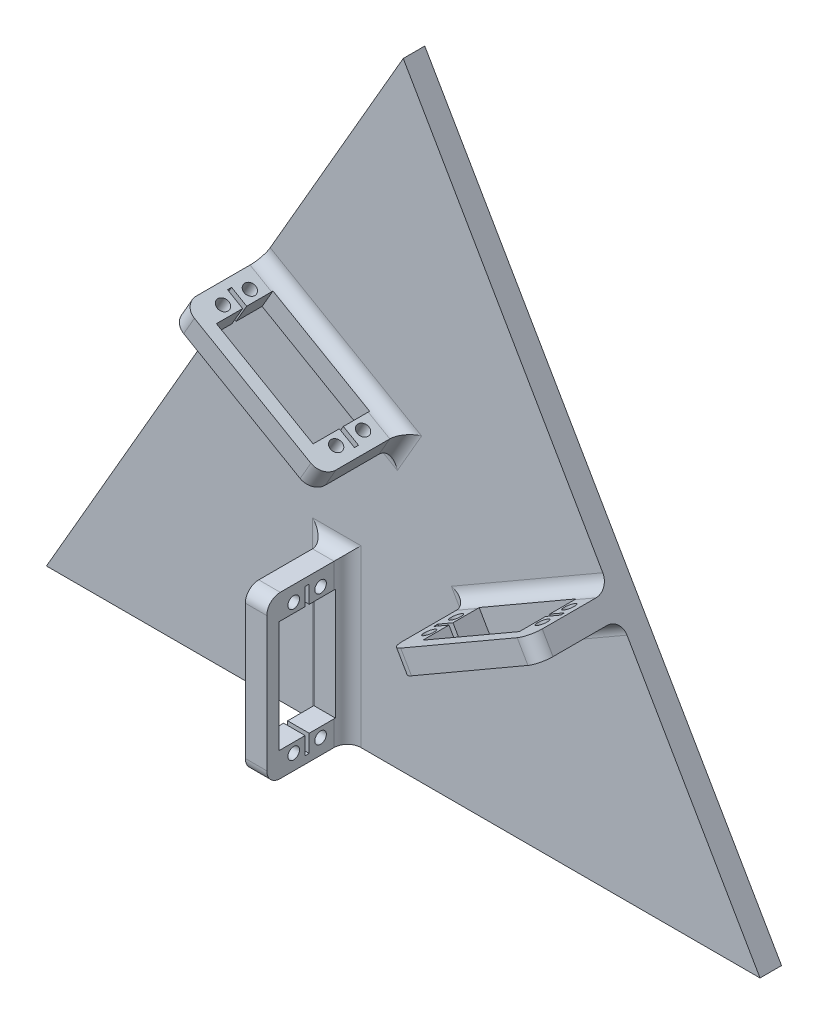
SolidWorks part; units mm, degrees
ref_plane "Front Plane" through (0, 0, 0) normal (1, 0, 0) x (0, 1, 0)
ref_plane "Top Plane" through (0, 0, 0) normal (0, 0, 1) x (0, 1, 0)
ref_plane "Right Plane" through (0, 0, 0) normal (0, 1, 0) x (-1, 0, 0)
sketch "Sketch1" plane through (0, 0, 0) normal (0, 0, 1) x (0, 1, 0)
  line L0 (0, 0) -> (49.7618, 86.19)
  line L1 (49.7618, 86.19) -> (99.5236, 0)
  line L2 (99.5236, 0) -> (0, 0)
  line L3 (63.1745, 109.4215) -> (49.7618, 86.19)
  line L4 (63.1745, 109.4215) -> (112.9364, 80.6915)
  line L5 (112.9364, 80.6915) -> (82.9364, 28.73)
  line L6 (99.5236, 0) -> (112.9364, -23.2315)
  line L7 (112.9364, -23.2315) -> (63.1745, -51.9615)
  line L8 (63.1745, -51.9615) -> (33.1745, 0)
  line L9 (0, 0) -> (-26.8255, 0)
  line L10 (-26.8255, 0) -> (-26.8255, 57.46)
  line L11 (-26.8255, 57.46) -> (33.1745, 57.46)
  line L12 (88.0555, 95.0565) -> (18.5216, -25.3796) construction
  line L13 (88.0555, -37.5965) -> (-9.2616, 130.9616) construction
  line L14 (-26.8255, 28.73) -> (138.1161, 28.73) construction
  dimension "D1" = 28.73
  dimension "D3" = 60
extrude "Boss-Extrude1" add sketch "Sketch1" along normal blind 8 contours L5 L4 L3 L1 | L11 L10 L9 L0 | L8 L7 L6 L2 | L2 L0 L1 region at (-32.3891, -4.0628, 0) region at (19.713, 73.5053, 0) region at (-73.5139, 79.843, 0)
sketch "Sketch2" plane through (0, 0, 8) normal (0, 0, 1) x (1, 0, 0)
  line L18 (-80.6915, 112.9364) -> (-28.73, 82.9364)
  line L19 (-28.73, 82.9364) -> (-32.73, 76.0082)
  line L20 (-32.73, 76.0082) -> (-84.6915, 106.0082)
  line L21 (-109.4215, 63.1745) -> (-80.6915, 112.9364) construction
  line L22 (-84.6915, 106.0082) -> (-80.6915, 112.9364)
  line L23 (51.9615, 63.1745) -> (0, 33.1745)
  line L24 (0, 33.1745) -> (-4, 40.1027)
  line L25 (-4, 40.1027) -> (47.9615, 70.1027)
  line L26 (23.2315, 112.9364) -> (51.9615, 63.1745) construction
  line L27 (47.9615, 70.1027) -> (51.9615, 63.1745)
  line L28 (-57.46, -26.8255) -> (-57.46, 33.1745)
  line L29 (-57.46, 33.1745) -> (-49.46, 33.1745)
  line L30 (-49.46, 33.1745) -> (-49.46, -26.8255)
  line L31 (0, -26.8255) -> (-57.46, -26.8255) construction
  line L32 (-49.46, -26.8255) -> (-57.46, -26.8255)
  line M5 (-28.73, 82.9364) -> (-80.6915, 112.9364)
  line M6 (-80.6915, 112.9364) -> (-109.4215, 63.1745)
  line M8 (-57.46, 33.1745) -> (-57.46, -26.8255)
  line M9 (-57.46, -26.8255) -> (0, -26.8255)
  line M11 (0, 33.1745) -> (51.9615, 63.1745)
  line M12 (51.9615, 63.1745) -> (23.2315, 112.9364)
  dimension "D1" = 8
extrude "Boss-Extrude2" add sketch "Sketch2" along normal blind 30 contours L20 L19 M5 M6 | L25 L24 M11 M12 | L30 L29 M8 M9 region at (-56.7108, 94.4723, 8) region at (23.9808, 51.6386, 8) region at (-53.46, 3.1745, 8)
sketch "Sketch3" plane through (-135.5994, 135.3999, 0) normal (-0.5, -0.866, 0) x (0.866, -0.5, 0)
  line L0 (109.5334, 23.75) -> (116.0334, 23.75)
  line L1 (64.4834, 28) -> (113.0834, 28) construction
  line L2 (64.4834, 28) -> (64.4834, 18) construction
  line L3 (64.4834, 18) -> (113.0834, 18) construction
  line L4 (113.0834, 28) -> (113.0834, 18) construction
  line L5 (88.7834, 38) -> (88.7834, 8) construction
  line L6 (68.0334, 12.5) -> (109.5334, 12.5)
  line L9 (68.0334, 12.5) -> (68.0334, 33.5)
  line L10 (68.0334, 33.5) -> (109.5334, 33.5)
  line L11 (109.5334, 12.5) -> (109.5334, 33.5)
  line L12 (58.7834, 23) -> (88.7834, 23) construction
  line L15 (68.0334, 12.5) -> (109.5334, 33.5) construction
  line L16 (68.0334, 33.5) -> (109.5334, 12.5) construction
  line L17 (61.5334, 23.75) -> (68.0334, 23.75)
  line L18 (61.5334, 23.75) -> (61.5334, 22.25)
  line L19 (61.5334, 22.25) -> (68.0334, 22.25)
  line L20 (116.0334, 23.75) -> (116.0334, 22.25)
  line L21 (109.5334, 22.25) -> (116.0334, 22.25)
  line L22 (118.7834, 38) -> (58.7834, 38) construction
  line L23 (58.7834, 38) -> (58.7834, 8) construction
  circle A0 centre (64.4834, 28) radius 2.15
  circle A1 centre (64.4834, 18) radius 2.15
  circle A2 centre (113.0834, 18) radius 2.15
  circle A3 centre (113.0834, 28) radius 2.15
  point P10 (64, 38)
  point P13 (34, 23)
  point P18 (0, 0)
  point P19 (64, 23)
  point P20 (88.7834, 28)
  point P21 (64.4834, 23)
  point P22 (88.7834, 23)
  point P31 (116.0334, 23)
  dimension "D1" = 4.3
  dimension "D2" = 10
  dimension "D3" = 48.6
  dimension "D4" = 41.5
  dimension "D5" = 21
  dimension "D6" = 1.5
  dimension "D7" = 6.5
extrude "Cut-Extrude1" cut sketch "Sketch3" against normal up to next contours L6 L11 L10 L9 | A0 | A1 | A2 | A3 | L11 L21 L20 L0 | L18 L19 L9 L17 region at (-37.9262, 79.0082, 23) region at (-58.7108, 91.0082, 23) region at (-79.4954, 103.0082, 23) region at (-79.7552, 103.1582, 28) region at (-79.7552, 103.1582, 18) region at (-37.6663, 78.8582, 18) region at (-37.6663, 78.8582, 28)
sketch "Sketch4" plane through (0.0029, 42.4138, 0) normal (-0.5, 0.866, 0) x (-0.866, -0.5, 0)
  line L0 (-25.3778, 38) -> (-25.3778, 8) construction
  line L3 (-55.3778, 23) -> (4.6222, 23) construction
  line L6 (-4.6278, 22.25) -> (1.8722, 22.25)
  line L7 (-49.6778, 18) -> (-1.0778, 18) construction
  line L8 (-49.6778, 18) -> (-49.6778, 28) construction
  line L9 (-49.6778, 28) -> (-1.0778, 28) construction
  line L10 (-1.0778, 18) -> (-1.0778, 28) construction
  line L11 (-49.6778, 18) -> (-1.0778, 28) construction
  line L12 (-49.6778, 28) -> (-1.0778, 18) construction
  line L13 (-46.1278, 12.5) -> (-4.6278, 12.5)
  line L14 (-46.1278, 12.5) -> (-46.1278, 33.5)
  line L15 (-46.1278, 33.5) -> (-4.6278, 33.5)
  line L16 (-4.6278, 12.5) -> (-4.6278, 33.5)
  line L17 (-46.1278, 12.5) -> (-4.6278, 33.5) construction
  line L18 (-46.1278, 33.5) -> (-4.6278, 12.5) construction
  line L19 (-52.6278, 23.75) -> (-46.1278, 23.75)
  line L20 (-52.6278, 23.75) -> (-52.6278, 22.25)
  line L21 (-52.6278, 22.25) -> (-46.1278, 22.25)
  line L22 (1.8722, 23.75) -> (1.8722, 22.25)
  line L23 (-4.6278, 23.75) -> (1.8722, 23.75)
  line L24 (4.6222, 38) -> (-55.3778, 38) construction
  line L25 (-55.3778, 38) -> (-55.3778, 8) construction
  circle A0 centre (-49.6778, 28) radius 2.15
  circle A1 centre (-49.6778, 18) radius 2.15
  circle A2 centre (-1.0778, 18) radius 2.15
  circle A3 centre (-1.0778, 28) radius 2.15
  point P2 (-39.923, 38)
  point P5 (-39.923, 22.1952)
  point P8 (-69.923, 23)
  point P11 (-15.623, 17.2063)
  point P12 (-25.3778, 23)
  point P21 (-25.3778, 23)
  point P30 (1.8722, 23)
  point P34 (-39.923, 23)
  dimension "D3" = 4.3
  dimension "D1" = 10
  dimension "D2" = 48.6
  dimension "D4" = 41.5
  dimension "D5" = 21
  dimension "D6" = 1.5
  dimension "D7" = 6.5
extrude "Cut-Extrude2" cut sketch "Sketch4" against normal up to next contours L13 L16 L15 L14 | A0 | A1 | L20 L21 L14 L19 | A2 | A3 | L23 L16 L6 L22 region at (1.1962, 43.1027, 23) region at (21.9808, 55.1027, 23) region at (42.7654, 67.1027, 23) region at (43.0252, 67.2527, 28) region at (43.0252, 67.2527, 18) region at (0.9363, 42.9527, 18) region at (0.9363, 42.9527, 28)
sketch "Sketch5" plane through (-49.46, -65.1325, 0) normal (1, 0, 0) x (0, 1, 0)
  line L0 (68.307, 38) -> (68.307, 8) construction
  line L3 (38.307, 23) -> (98.307, 23) construction
  line L6 (89.057, 23.75) -> (95.557, 23.75)
  line L7 (44.007, 18) -> (92.607, 18) construction
  line L8 (44.007, 18) -> (44.007, 28) construction
  line L9 (44.007, 28) -> (92.607, 28) construction
  line L10 (92.607, 18) -> (92.607, 28) construction
  line L11 (44.007, 18) -> (92.607, 28) construction
  line L12 (44.007, 28) -> (92.607, 18) construction
  line L13 (47.557, 12.5) -> (89.057, 12.5)
  line L14 (47.557, 12.5) -> (47.557, 33.5)
  line L15 (47.557, 33.5) -> (89.057, 33.5)
  line L16 (89.057, 12.5) -> (89.057, 33.5)
  line L17 (47.557, 12.5) -> (89.057, 33.5) construction
  line L18 (47.557, 33.5) -> (89.057, 12.5) construction
  line L19 (41.057, 23.75) -> (47.557, 23.75)
  line L20 (41.057, 23.75) -> (41.057, 22.25)
  line L21 (41.057, 22.25) -> (47.557, 22.25)
  line L22 (95.557, 23.75) -> (95.557, 22.25)
  line L23 (89.057, 22.25) -> (95.557, 22.25)
  line L24 (98.307, 38) -> (38.307, 38) construction
  line L25 (38.307, 38) -> (38.307, 8) construction
  circle A0 centre (44.007, 28) radius 2.15
  circle A1 centre (44.007, 18) radius 2.15
  circle A2 centre (92.607, 18) radius 2.15
  circle A3 centre (92.607, 28) radius 2.15
  point P2 (64, 38)
  point P5 (64, 21.9309)
  point P8 (34, 23)
  point P11 (88.3, 10.8406)
  point P12 (68.307, 23)
  point P21 (68.307, 23)
  point P30 (95.557, 23)
  point P31 (64, 23)
  dimension "D3" = 4.3
  dimension "D1" = 48.6
  dimension "D2" = 10
  dimension "D4" = 41.5
  dimension "D5" = 21
  dimension "D6" = 1.5
  dimension "D7" = 6.5
extrude "Cut-Extrude3" cut sketch "Sketch5" against normal up to next contours L13 L16 L15 L14 | A0 | A1 | L20 L21 L14 L19 | A2 | L16 L23 L22 L6 | A3 region at (-49.46, 27.1745, 23) region at (-49.46, 3.1745, 23) region at (-49.46, -20.8255, 23) region at (-49.46, -21.1255, 28) region at (-49.46, -21.1255, 18) region at (-49.46, 27.4745, 18) region at (-49.46, 27.4745, 28)
sketch "Sketch6" plane through (0, 0, 8) normal (0, 0, 1) x (1, 0, 0)
  line L0 (-109.4215, 63.1745) -> (-57.46, -26.8255)
  line L1 (0, -26.8255) -> (51.9615, 63.1745)
  line L2 (-80.6915, 112.9364) -> (23.2315, 112.9364)
  line L3 (-80.6915, 112.9364) -> (-28.73, 82.9364)
  line L4 (-28.73, 82.9364) -> (23.2315, 112.9364)
  line L5 (-109.4215, 63.1745) -> (-57.46, 33.1745)
  line L6 (-57.46, 33.1745) -> (-57.46, -26.8255)
  line L7 (0, -26.8255) -> (0, 33.1745)
  line L8 (0, 33.1745) -> (51.9615, 63.1745)
  line L9 (-109.4215, 63.1745) -> (-161.383, -26.8255)
  line L10 (-161.383, -26.8255) -> (-57.46, -26.8255)
  line L11 (0, -26.8255) -> (103.923, -26.8255)
  line L12 (103.923, -26.8255) -> (51.9615, 63.1745)
  line L13 (23.2315, 112.9364) -> (-28.73, 202.9364)
  line L14 (-28.73, 202.9364) -> (-80.6915, 112.9364)
  line M7 (-109.4215, 63.1745) -> (-57.46, 33.1745)
  line M11 (0, -26.8255) -> (0, 33.1745)
  line M15 (23.2315, 112.9364) -> (-28.73, 82.9364)
extrude "Boss-Extrude3" add sketch "Sketch6" against normal up to surface (8 mm away) contours L9 L10 L0 | L6 L0 M7 | L8 L1 M11 | L11 L12 L1 | L2 L3 M15 | L13 L14 L2 region at (-74.7805, 23.1745, 8) region at (-109.4215, 3.1745, 8) region at (17.3205, 23.1745, 8) region at (51.9615, 3.1745, 8) region at (-28.73, 142.9364, 8) region at (-28.73, 102.9364, 8) up to face at (-28.73, 49.7618, 0)
fillet "Fillet1" radius 5 15 edges at (21.9808, 55.1027, 8) (25.9808, 48.1745, 8) (-2, 36.6386, 8) (-53.46, 33.1745, 8) (-57.46, 3.1745, 8) (-49.46, 3.1745, 8) (-58.7108, 91.0082, 8) (-30.73, 79.4723, 8) (-54.7108, 97.9364, 8) (-30.73, 79.4723, 38) (-82.6915, 109.4723, 38) (49.9615, 66.6386, 38) (-2, 36.6386, 38) (-53.46, 33.1745, 38) (-53.46, -26.8255, 38)
